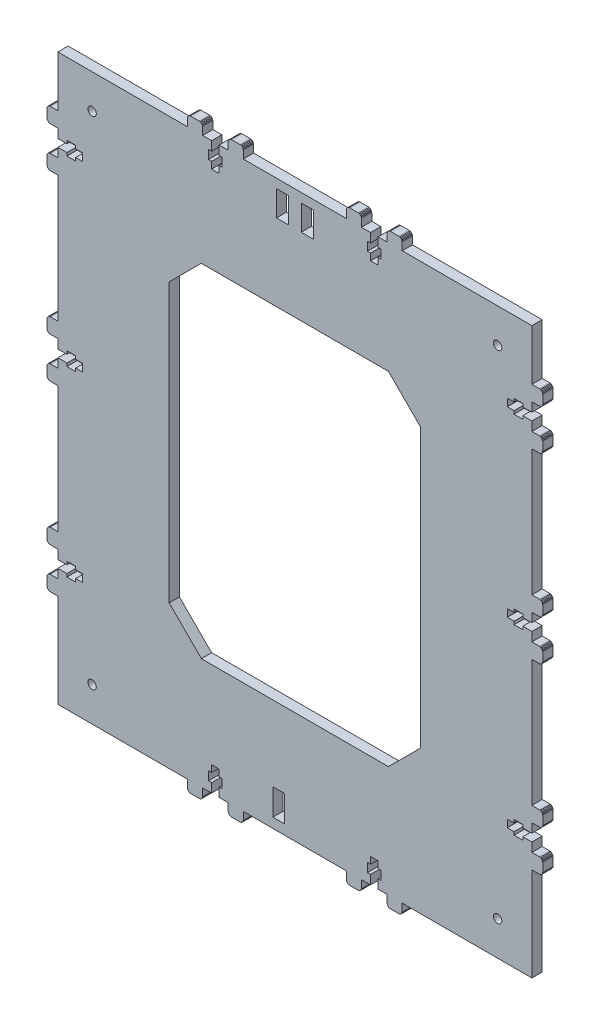
SolidWorks part; units mm, degrees
ref_plane "Plano frontal" through (0, 0, 0) normal (0, 0, 1) x (1, 0, 0)
ref_plane "Plano superior" through (0, 0, 0) normal (0, 1, 0) x (1, 0, 0)
ref_plane "Plano direito" through (0, 0, 0) normal (1, 0, 0) x (0, 0, -1)
sketch "Model" plane through (0, 0, 0) normal (0, 0, 1) x (1, 0, 0)
  line L0 (136.5926, 337.8518) -> (136.5926, 343.1518)
  line L1 (136.5926, 332.7518) -> (138.3926, 332.7518)
  line L2 (138.3926, 337.8518) -> (136.5926, 337.8518)
  line L3 (130.3926, 337.8518) -> (130.3926, 332.7518)
  line L4 (234.6925, 13.2519) -> (229.3925, 13.2519)
  line L5 (132.1926, 332.7518) -> (132.1926, 328.8018)
  line L6 (319.1925, 280.8519) -> (319.1925, 207.0019)
  line L7 (47.6926, 82.0519) -> (47.6926, 80.2519)
  line L8 (56.7426, 86.4519) -> (52.7926, 86.4519)
  line L9 (52.7926, 80.2519) -> (52.7926, 82.0519)
  line L10 (42.3926, 91.7519) -> (38.0426, 91.7519)
  line L11 (42.3926, 67.9519) -> (38.0426, 67.9519)
  line L12 (52.7926, 88.2519) -> (47.6926, 88.2519)
  line L13 (56.7426, 82.0519) -> (56.7426, 86.4519)
  line L14 (229.3925, 337.8518) -> (229.3925, 343.1518)
  line L15 (319.1925, 174.4019) -> (319.1925, 100.5519)
  line L16 (224.9925, 343.1518) -> (224.9925, 337.8518)
  line L17 (52.7926, 299.3519) -> (52.7926, 301.1519)
  line L18 (229.3925, 332.7518) -> (231.1925, 332.7518)
  line L19 (132.1926, 343.1518) -> (132.1926, 337.8518)
  line L20 (56.7426, 294.9519) -> (56.7426, 299.3519)
  line L21 (223.1925, 337.8518) -> (223.1925, 332.7518)
  line L22 (47.6926, 88.2519) -> (47.6926, 86.4519)
  line L23 (47.6926, 80.2519) -> (52.7926, 80.2519)
  line L24 (42.3926, 13.2519) -> (42.3926, 67.9519)
  line L25 (52.7926, 293.1519) -> (52.7926, 294.9519)
  line L26 (319.1925, 13.2519) -> (243.4925, 13.2519)
  line L27 (52.7926, 188.5019) -> (56.7426, 188.5019)
  line L28 (56.7426, 192.9019) -> (52.7926, 192.9019)
  line L29 (313.8925, 301.1519) -> (308.7925, 301.1519)
  line L30 (313.8925, 299.3519) -> (313.8925, 301.1519)
  line L31 (304.8425, 294.9519) -> (308.7925, 294.9519)
  line L32 (47.6926, 293.1519) -> (52.7926, 293.1519)
  line L33 (138.3926, 18.5519) -> (138.3926, 23.6519)
  line L34 (136.5926, 18.5519) -> (138.3926, 18.5519)
  line L35 (132.1926, 27.6019) -> (132.1926, 23.6519)
  line L36 (138.3926, 23.6519) -> (136.5926, 23.6519)
  line L37 (126.8926, 13.2519) -> (126.8926, 8.902)
  line L38 (150.6926, 13.2519) -> (150.6926, 8.902)
  line L39 (130.3926, 23.6519) -> (130.3926, 18.5519)
  line L40 (42.3926, 198.2019) -> (38.0426, 198.2019)
  line L41 (319.1925, 67.9519) -> (319.1925, 13.2519)
  line L42 (132.1926, 18.5519) -> (132.1926, 13.2519)
  line L43 (132.1926, 23.6519) -> (130.3926, 23.6519)
  line L44 (130.3926, 18.5519) -> (132.1926, 18.5519)
  line L45 (42.3926, 313.4519) -> (42.3926, 343.1518)
  line L46 (42.3926, 188.5019) -> (47.6926, 188.5019)
  line L47 (47.6926, 192.9019) -> (42.3926, 192.9019)
  line L48 (47.6926, 186.7019) -> (52.7926, 186.7019)
  line L49 (231.1925, 18.5519) -> (231.1925, 23.6519)
  line L50 (229.3925, 18.5519) -> (231.1925, 18.5519)
  line L51 (224.9925, 27.6019) -> (224.9925, 23.6519)
  line L52 (308.7925, 301.1519) -> (308.7925, 299.3519)
  line L53 (319.1925, 289.6519) -> (323.5425, 289.6519)
  line L54 (319.1925, 313.4518) -> (323.5425, 313.4518)
  line L55 (308.7925, 293.1519) -> (313.8925, 293.1519)
  line L56 (304.8425, 299.3519) -> (304.8425, 294.9519)
  line L57 (304.8425, 82.0519) -> (308.7925, 82.0519)
  line L58 (304.8425, 192.9019) -> (304.8425, 188.5019)
  line L59 (118.0926, 13.2519) -> (42.3926, 13.2519)
  line L60 (319.1925, 192.9019) -> (313.8925, 192.9019)
  line L61 (319.1925, 294.9519) -> (319.1925, 289.6519)
  line L62 (319.1925, 304.6519) -> (319.1925, 299.3519)
  line L63 (308.7925, 294.9519) -> (308.7925, 293.1519)
  line L64 (313.8925, 293.1519) -> (313.8925, 294.9519)
  line L65 (308.7925, 192.9019) -> (304.8425, 192.9019)
  line L66 (319.1925, 198.2019) -> (319.1925, 192.9019)
  line L67 (231.1925, 337.8518) -> (229.3925, 337.8518)
  line L68 (313.8925, 82.0519) -> (319.1925, 82.0519)
  line L69 (308.7925, 82.0519) -> (308.7925, 80.2519)
  line L70 (210.8925, 343.1518) -> (210.8925, 347.5018)
  line L71 (231.1925, 332.7518) -> (231.1925, 337.8518)
  line L72 (224.9925, 337.8518) -> (223.1925, 337.8518)
  line L73 (47.6926, 86.4519) -> (42.3926, 86.4519)
  line L74 (52.7926, 86.4519) -> (52.7926, 88.2519)
  line L75 (319.1925, 76.7519) -> (323.5425, 76.7519)
  line L76 (319.1925, 100.5519) -> (323.5425, 100.5519)
  line L77 (308.7925, 80.2519) -> (313.8925, 80.2519)
  line L78 (52.7926, 301.1519) -> (47.6926, 301.1519)
  line L79 (229.3925, 13.2519) -> (229.3925, 18.5519)
  line L80 (42.3926, 192.9019) -> (42.3926, 198.2019)
  line L81 (52.7926, 186.7019) -> (52.7926, 188.5019)
  line L82 (47.6926, 188.5019) -> (47.6926, 186.7019)
  line L83 (42.3926, 82.0519) -> (47.6926, 82.0519)
  line L84 (52.7926, 82.0519) -> (56.7426, 82.0519)
  line L85 (313.8925, 188.5019) -> (319.1925, 188.5019)
  line L86 (308.7925, 188.5019) -> (308.7925, 186.7019)
  line L87 (313.8925, 186.7019) -> (313.8925, 188.5019)
  line L88 (313.8925, 194.7019) -> (308.7925, 194.7019)
  line L89 (132.1926, 13.2519) -> (126.8926, 13.2519)
  line L90 (224.9925, 13.2519) -> (219.6925, 13.2519)
  line L91 (47.6926, 294.9519) -> (47.6926, 293.1519)
  line L92 (231.1925, 23.6519) -> (229.3925, 23.6519)
  line L93 (136.5926, 13.2519) -> (136.5926, 18.5519)
  line L94 (136.5926, 23.6519) -> (136.5926, 27.6019)
  line L95 (141.8926, 13.2519) -> (136.5926, 13.2519)
  line L96 (56.7426, 188.5019) -> (56.7426, 192.9019)
  line L97 (47.6926, 194.7019) -> (47.6926, 192.9019)
  line L98 (52.7926, 194.7019) -> (47.6926, 194.7019)
  line L99 (319.1925, 82.0519) -> (319.1925, 76.7519)
  line L100 (313.8925, 88.2519) -> (308.7925, 88.2519)
  line L101 (132.1926, 337.8518) -> (130.3926, 337.8518)
  line L102 (136.5926, 328.8018) -> (136.5926, 332.7518)
  line L103 (130.3926, 332.7518) -> (132.1926, 332.7518)
  line L104 (141.8926, 343.1518) -> (141.8926, 347.5018)
  line L105 (229.3925, 343.1518) -> (234.6925, 343.1518)
  line L106 (136.5926, 27.6019) -> (132.1926, 27.6019)
  line L107 (42.3926, 294.9519) -> (47.6926, 294.9519)
  line L108 (52.7926, 294.9519) -> (56.7426, 294.9519)
  line L109 (56.7426, 299.3519) -> (52.7926, 299.3519)
  line L110 (42.3926, 86.4519) -> (42.3926, 91.7519)
  line L111 (42.3926, 100.5519) -> (42.3926, 174.4019)
  line L112 (42.3926, 207.0019) -> (42.3926, 280.8519)
  line L113 (42.3926, 76.7519) -> (42.3926, 82.0519)
  line L114 (223.1925, 23.6519) -> (223.1925, 18.5519)
  line L115 (229.3925, 27.6019) -> (224.9925, 27.6019)
  line L116 (224.9925, 18.5519) -> (224.9925, 13.2519)
  line L117 (304.8425, 188.5019) -> (308.7925, 188.5019)
  line L118 (308.7925, 194.7019) -> (308.7925, 192.9019)
  line L119 (319.1925, 183.2019) -> (323.5425, 183.2019)
  line L120 (319.1925, 207.0019) -> (323.5425, 207.0019)
  line L121 (308.7925, 186.7019) -> (313.8925, 186.7019)
  line L122 (138.3926, 332.7518) -> (138.3926, 337.8518)
  line L123 (132.1926, 328.8018) -> (136.5926, 328.8018)
  line L124 (219.6925, 13.2519) -> (219.6925, 8.902)
  line L125 (243.4925, 13.2519) -> (243.4925, 8.902)
  line L126 (229.3925, 328.8018) -> (229.3925, 332.7518)
  line L127 (234.6925, 343.1518) -> (234.6925, 347.5018)
  line L128 (42.3926, 183.2019) -> (42.3926, 188.5019)
  line L129 (319.1925, 299.3519) -> (313.8925, 299.3519)
  line L130 (308.7925, 299.3519) -> (304.8425, 299.3519)
  line L131 (319.1925, 188.5019) -> (319.1925, 183.2019)
  line L132 (313.8925, 294.9519) -> (319.1925, 294.9519)
  line L133 (52.7926, 192.9019) -> (52.7926, 194.7019)
  line L134 (319.1925, 91.7519) -> (319.1925, 86.4519)
  line L135 (229.3925, 23.6519) -> (229.3925, 27.6019)
  line L136 (136.5926, 343.1518) -> (141.8926, 343.1518)
  line L137 (150.6926, 343.1518) -> (210.8925, 343.1518)
  line L138 (219.6925, 343.1518) -> (224.9925, 343.1518)
  line L139 (42.3926, 174.4019) -> (38.0426, 174.4019)
  line L140 (223.1925, 18.5519) -> (224.9925, 18.5519)
  line L141 (47.6926, 301.1519) -> (47.6926, 299.3519)
  line L142 (47.6926, 299.3519) -> (42.3926, 299.3519)
  line L143 (42.3926, 299.3519) -> (42.3926, 304.6519)
  line L144 (210.8925, 13.2519) -> (150.6926, 13.2519)
  line L145 (42.3926, 304.6519) -> (38.0426, 304.6519)
  line L146 (243.4925, 343.1518) -> (319.1925, 343.1518)
  line L147 (319.1925, 343.1518) -> (319.1925, 313.4518)
  line L148 (223.1925, 332.7518) -> (224.9925, 332.7518)
  line L149 (224.9925, 332.7518) -> (224.9925, 328.8018)
  line L150 (224.9925, 328.8018) -> (229.3925, 328.8018)
  line L151 (319.1925, 86.4519) -> (313.8925, 86.4519)
  line L152 (313.8925, 86.4519) -> (313.8925, 88.2519)
  line L153 (308.7925, 88.2519) -> (308.7925, 86.4519)
  line L154 (308.7925, 86.4519) -> (304.8425, 86.4519)
  line L155 (304.8425, 86.4519) -> (304.8425, 82.0519)
  line L156 (224.9925, 23.6519) -> (223.1925, 23.6519)
  line L157 (42.3926, 343.1518) -> (118.0926, 343.1518)
  line L158 (118.0926, 343.1518) -> (118.0926, 347.5018)
  line L159 (124.8926, 349.5018) -> (125.4102, 349.4337)
  line L160 (125.4102, 349.4337) -> (125.8926, 349.2339)
  line L161 (125.8926, 349.2339) -> (126.3068, 348.9161)
  line L162 (126.3068, 348.9161) -> (126.6246, 348.5018)
  line L163 (126.6246, 348.5018) -> (126.8244, 348.0195)
  line L164 (126.8926, 347.5018) -> (126.8926, 343.1518)
  line L165 (126.8244, 348.0195) -> (126.8926, 347.5018)
  line L166 (141.8926, 347.5018) -> (141.9607, 348.0195)
  line L167 (141.9607, 348.0195) -> (142.1605, 348.5018)
  line L168 (142.1605, 348.5018) -> (142.4783, 348.9161)
  line L169 (142.4783, 348.9161) -> (142.8926, 349.2339)
  line L170 (142.8926, 349.2339) -> (143.3749, 349.4337)
  line L171 (143.8926, 349.5018) -> (148.6926, 349.5018)
  line L172 (143.3749, 349.4337) -> (143.8926, 349.5018)
  line L173 (150.6926, 347.5018) -> (150.6926, 343.1518)
  line L174 (150.6926, 347.5018) -> (150.6244, 348.0195)
  line L175 (150.6244, 348.0195) -> (150.4246, 348.5018)
  line L176 (150.4246, 348.5018) -> (150.1068, 348.9161)
  line L177 (150.1068, 348.9161) -> (149.6926, 349.2339)
  line L178 (149.6926, 349.2339) -> (149.2102, 349.4337)
  line L179 (149.2102, 349.4337) -> (148.6926, 349.5018)
  line L180 (118.0926, 347.5018) -> (118.1607, 348.0195)
  line L181 (118.1607, 348.0195) -> (118.3605, 348.5018)
  line L182 (118.3605, 348.5018) -> (118.6784, 348.9161)
  line L183 (118.6784, 348.9161) -> (119.0926, 349.2339)
  line L184 (119.0926, 349.2339) -> (119.5749, 349.4337)
  line L185 (120.0926, 349.5018) -> (124.8926, 349.5018)
  line L186 (119.5749, 349.4337) -> (120.0926, 349.5018)
  line L187 (234.6925, 347.5018) -> (234.7607, 348.0195)
  line L188 (234.7607, 348.0195) -> (234.9605, 348.5018)
  line L189 (234.9605, 348.5018) -> (235.2783, 348.9161)
  line L190 (235.2783, 348.9161) -> (235.6925, 349.2339)
  line L191 (235.6925, 349.2339) -> (236.1749, 349.4337)
  line L192 (236.6925, 349.5018) -> (241.4925, 349.5018)
  line L193 (236.1749, 349.4337) -> (236.6925, 349.5018)
  line L194 (243.4925, 347.5018) -> (243.4925, 343.1518)
  line L195 (243.4925, 347.5018) -> (243.4244, 348.0195)
  line L196 (243.4244, 348.0195) -> (243.2246, 348.5018)
  line L197 (243.2246, 348.5018) -> (242.9067, 348.9161)
  line L198 (242.9067, 348.9161) -> (242.4925, 349.2339)
  line L199 (242.4925, 349.2339) -> (242.0102, 349.4337)
  line L200 (242.0102, 349.4337) -> (241.4925, 349.5018)
  line L201 (219.6925, 347.5018) -> (219.6925, 343.1518)
  line L202 (219.6925, 347.5018) -> (219.6244, 348.0195)
  line L203 (219.6244, 348.0195) -> (219.4246, 348.5018)
  line L204 (219.4246, 348.5018) -> (219.1068, 348.9161)
  line L205 (219.1068, 348.9161) -> (218.6925, 349.2339)
  line L206 (218.6925, 349.2339) -> (218.2102, 349.4337)
  line L207 (218.2102, 349.4337) -> (217.6925, 349.5018)
  line L208 (210.8925, 347.5018) -> (210.9607, 348.0195)
  line L209 (210.9607, 348.0195) -> (211.1605, 348.5018)
  line L210 (211.1605, 348.5018) -> (211.4783, 348.9161)
  line L211 (211.4783, 348.9161) -> (211.8925, 349.2339)
  line L212 (211.8925, 349.2339) -> (212.3749, 349.4337)
  line L213 (212.8925, 349.5018) -> (217.6925, 349.5018)
  line L214 (212.3749, 349.4337) -> (212.8925, 349.5018)
  line L215 (210.8925, 8.902) -> (210.8925, 13.2519)
  line L216 (210.8925, 8.902) -> (210.9607, 8.3843)
  line L217 (210.9607, 8.3843) -> (211.1605, 7.902)
  line L218 (211.1605, 7.902) -> (211.4783, 7.4877)
  line L219 (211.4783, 7.4877) -> (211.8925, 7.1699)
  line L220 (211.8925, 7.1699) -> (212.3749, 6.9701)
  line L221 (212.3749, 6.9701) -> (212.8925, 6.902)
  line L222 (219.6925, 8.902) -> (219.6244, 8.3843)
  line L223 (219.6244, 8.3843) -> (219.4246, 7.902)
  line L224 (219.4246, 7.902) -> (219.1067, 7.4877)
  line L225 (219.1067, 7.4877) -> (218.6925, 7.1699)
  line L226 (218.6925, 7.1699) -> (218.2102, 6.9701)
  line L227 (217.6925, 6.902) -> (212.8925, 6.902)
  line L228 (218.2102, 6.9701) -> (217.6925, 6.902)
  line L229 (323.5425, 174.4019) -> (319.1925, 174.4019)
  line L230 (323.5425, 174.4019) -> (324.0601, 174.47)
  line L231 (324.0601, 174.47) -> (324.5425, 174.6698)
  line L232 (324.5425, 174.6698) -> (324.9567, 174.9877)
  line L233 (324.9567, 174.9877) -> (325.2746, 175.4019)
  line L234 (325.2746, 175.4019) -> (325.4744, 175.8843)
  line L235 (325.4744, 175.8843) -> (325.5425, 176.4019)
  line L236 (325.5425, 93.7519) -> (325.4744, 93.2343)
  line L237 (325.4744, 93.2343) -> (325.2746, 92.7519)
  line L238 (325.2746, 92.7519) -> (324.9567, 92.3377)
  line L239 (324.9567, 92.3377) -> (324.5425, 92.0199)
  line L240 (324.5425, 92.0199) -> (324.0601, 91.8201)
  line L241 (323.5425, 91.7519) -> (319.1925, 91.7519)
  line L242 (324.0601, 91.8201) -> (323.5425, 91.7519)
  line L243 (36.0426, 93.7519) -> (36.0426, 98.5519)
  line L244 (36.0426, 93.7519) -> (36.1107, 93.2343)
  line L245 (36.1107, 93.2343) -> (36.3105, 92.7519)
  line L246 (36.3105, 92.7519) -> (36.6284, 92.3377)
  line L247 (36.6284, 92.3377) -> (37.0426, 92.0199)
  line L248 (37.0426, 92.0199) -> (37.525, 91.8201)
  line L249 (37.525, 91.8201) -> (38.0426, 91.7519)
  line L250 (38.0426, 67.9519) -> (37.525, 68.0201)
  line L251 (37.525, 68.0201) -> (37.0426, 68.2199)
  line L252 (37.0426, 68.2199) -> (36.6284, 68.5377)
  line L253 (36.6284, 68.5377) -> (36.3105, 68.9519)
  line L254 (36.3105, 68.9519) -> (36.1107, 69.4343)
  line L255 (36.0426, 69.9519) -> (36.0426, 74.7519)
  line L256 (36.1107, 69.4343) -> (36.0426, 69.9519)
  line L257 (38.0426, 76.7519) -> (42.3926, 76.7519)
  line L258 (38.0426, 76.7519) -> (37.525, 76.6838)
  line L259 (37.525, 76.6838) -> (37.0426, 76.484)
  line L260 (37.0426, 76.484) -> (36.6284, 76.1661)
  line L261 (36.6284, 76.1661) -> (36.3105, 75.7519)
  line L262 (36.3105, 75.7519) -> (36.1107, 75.2696)
  line L263 (36.1107, 75.2696) -> (36.0426, 74.7519)
  line L264 (36.0426, 306.6519) -> (36.0426, 311.4519)
  line L265 (36.0426, 306.6519) -> (36.1107, 306.1342)
  line L266 (36.1107, 306.1342) -> (36.3105, 305.6519)
  line L267 (36.3105, 305.6519) -> (36.6284, 305.2376)
  line L268 (36.6284, 305.2376) -> (37.0426, 304.9198)
  line L269 (37.0426, 304.9198) -> (37.525, 304.72)
  line L270 (37.525, 304.72) -> (38.0426, 304.6519)
  line L271 (325.5425, 69.9519) -> (325.4744, 69.4343)
  line L272 (325.4744, 69.4343) -> (325.2746, 68.9519)
  line L273 (325.2746, 68.9519) -> (324.9567, 68.5377)
  line L274 (324.9567, 68.5377) -> (324.5425, 68.2199)
  line L275 (324.5425, 68.2199) -> (324.0601, 68.0201)
  line L276 (323.5425, 67.9519) -> (319.1925, 67.9519)
  line L277 (324.0601, 68.0201) -> (323.5425, 67.9519)
  line L278 (124.8926, 6.902) -> (120.0926, 6.902)
  line L279 (124.8926, 6.902) -> (125.4102, 6.9701)
  line L280 (125.4102, 6.9701) -> (125.8926, 7.1699)
  line L281 (125.8926, 7.1699) -> (126.3068, 7.4877)
  line L282 (126.3068, 7.4877) -> (126.6246, 7.902)
  line L283 (126.6246, 7.902) -> (126.8244, 8.3843)
  line L284 (126.8244, 8.3843) -> (126.8926, 8.902)
  line L285 (118.0926, 8.902) -> (118.0926, 13.2519)
  line L286 (118.0926, 8.902) -> (118.1607, 8.3843)
  line L287 (118.1607, 8.3843) -> (118.3605, 7.902)
  line L288 (118.3605, 7.902) -> (118.6784, 7.4877)
  line L289 (118.6784, 7.4877) -> (119.0926, 7.1699)
  line L290 (119.0926, 7.1699) -> (119.5749, 6.9701)
  line L291 (119.5749, 6.9701) -> (120.0926, 6.902)
  line L292 (38.0426, 100.5519) -> (42.3926, 100.5519)
  line L293 (38.0426, 100.5519) -> (37.525, 100.4838)
  line L294 (37.525, 100.4838) -> (37.0426, 100.284)
  line L295 (37.0426, 100.284) -> (36.6284, 99.9661)
  line L296 (36.6284, 99.9661) -> (36.3105, 99.5519)
  line L297 (36.3105, 99.5519) -> (36.1107, 99.0696)
  line L298 (36.1107, 99.0696) -> (36.0426, 98.5519)
  line L299 (323.5425, 304.6519) -> (319.1925, 304.6519)
  line L300 (323.5425, 304.6519) -> (324.0601, 304.72)
  line L301 (324.0601, 304.72) -> (324.5425, 304.9198)
  line L302 (324.5425, 304.9198) -> (324.9567, 305.2376)
  line L303 (324.9567, 305.2376) -> (325.2746, 305.6519)
  line L304 (325.2746, 305.6519) -> (325.4744, 306.1342)
  line L305 (325.4744, 306.1342) -> (325.5425, 306.6519)
  line L306 (325.5425, 287.6519) -> (325.5425, 282.8519)
  line L307 (325.5425, 287.6519) -> (325.4744, 288.1695)
  line L308 (325.4744, 288.1695) -> (325.2746, 288.6519)
  line L309 (325.2746, 288.6519) -> (324.9567, 289.0661)
  line L310 (324.9567, 289.0661) -> (324.5425, 289.3839)
  line L311 (324.5425, 289.3839) -> (324.0601, 289.5837)
  line L312 (324.0601, 289.5837) -> (323.5425, 289.6519)
  line L313 (323.5425, 280.8519) -> (319.1925, 280.8519)
  line L314 (323.5425, 280.8519) -> (324.0601, 280.92)
  line L315 (324.0601, 280.92) -> (324.5425, 281.1198)
  line L316 (324.5425, 281.1198) -> (324.9567, 281.4377)
  line L317 (324.9567, 281.4377) -> (325.2746, 281.8519)
  line L318 (325.2746, 281.8519) -> (325.4744, 282.3342)
  line L319 (325.4744, 282.3342) -> (325.5425, 282.8519)
  line L320 (148.6926, 6.902) -> (143.8926, 6.902)
  line L321 (148.6926, 6.902) -> (149.2102, 6.9701)
  line L322 (149.2102, 6.9701) -> (149.6926, 7.1699)
  line L323 (149.6926, 7.1699) -> (150.1068, 7.4877)
  line L324 (150.1068, 7.4877) -> (150.4246, 7.902)
  line L325 (150.4246, 7.902) -> (150.6244, 8.3843)
  line L326 (150.6244, 8.3843) -> (150.6926, 8.902)
  line L327 (36.0426, 200.2019) -> (36.0426, 205.0019)
  line L328 (36.0426, 200.2019) -> (36.1107, 199.6843)
  line L329 (36.1107, 199.6843) -> (36.3105, 199.2019)
  line L330 (36.3105, 199.2019) -> (36.6284, 198.7877)
  line L331 (36.6284, 198.7877) -> (37.0426, 198.4698)
  line L332 (37.0426, 198.4698) -> (37.525, 198.27)
  line L333 (37.525, 198.27) -> (38.0426, 198.2019)
  line L334 (141.8926, 8.902) -> (141.8926, 13.2519)
  line L335 (141.8926, 8.902) -> (141.9607, 8.3843)
  line L336 (141.9607, 8.3843) -> (142.1605, 7.902)
  line L337 (142.1605, 7.902) -> (142.4783, 7.4877)
  line L338 (142.4783, 7.4877) -> (142.8926, 7.1699)
  line L339 (142.8926, 7.1699) -> (143.3749, 6.9701)
  line L340 (143.3749, 6.9701) -> (143.8926, 6.902)
  line L341 (38.0426, 207.0019) -> (42.3926, 207.0019)
  line L342 (38.0426, 207.0019) -> (37.525, 206.9337)
  line L343 (37.525, 206.9337) -> (37.0426, 206.7339)
  line L344 (37.0426, 206.7339) -> (36.6284, 206.4161)
  line L345 (36.6284, 206.4161) -> (36.3105, 206.0019)
  line L346 (36.3105, 206.0019) -> (36.1107, 205.5195)
  line L347 (36.1107, 205.5195) -> (36.0426, 205.0019)
  line L348 (38.0426, 313.4519) -> (42.3926, 313.4519)
  line L349 (38.0426, 313.4519) -> (37.525, 313.3837)
  line L350 (37.525, 313.3837) -> (37.0426, 313.1839)
  line L351 (37.0426, 313.1839) -> (36.6284, 312.8661)
  line L352 (36.6284, 312.8661) -> (36.3105, 312.4519)
  line L353 (36.3105, 312.4519) -> (36.1107, 311.9695)
  line L354 (36.1107, 311.9695) -> (36.0426, 311.4519)
  line L355 (38.0426, 289.6519) -> (42.3926, 289.6519)
  line L356 (38.0426, 289.6519) -> (37.525, 289.5837)
  line L357 (37.525, 289.5837) -> (37.0426, 289.3839)
  line L358 (37.0426, 289.3839) -> (36.6284, 289.0661)
  line L359 (36.6284, 289.0661) -> (36.3105, 288.6519)
  line L360 (36.3105, 288.6519) -> (36.1107, 288.1695)
  line L361 (36.1107, 288.1695) -> (36.0426, 287.6519)
  line L362 (323.5425, 313.4518) -> (324.0601, 313.3837)
  line L363 (324.0601, 313.3837) -> (324.5425, 313.1839)
  line L364 (324.5425, 313.1839) -> (324.9567, 312.8661)
  line L365 (324.9567, 312.8661) -> (325.2746, 312.4518)
  line L366 (325.2746, 312.4518) -> (325.4744, 311.9695)
  line L367 (325.5425, 311.4518) -> (325.5425, 306.6519)
  line L368 (325.4744, 311.9695) -> (325.5425, 311.4518)
  line L369 (236.6925, 6.902) -> (236.1749, 6.9701)
  line L370 (236.1749, 6.9701) -> (235.6925, 7.1699)
  line L371 (235.6925, 7.1699) -> (235.2783, 7.4877)
  line L372 (235.2783, 7.4877) -> (234.9605, 7.902)
  line L373 (234.9605, 7.902) -> (234.7607, 8.3843)
  line L374 (234.6925, 8.902) -> (234.6925, 13.2519)
  line L375 (234.7607, 8.3843) -> (234.6925, 8.902)
  line L376 (325.5425, 74.7519) -> (325.5425, 69.9519)
  line L377 (325.5425, 74.7519) -> (325.4744, 75.2696)
  line L378 (325.4744, 75.2696) -> (325.2746, 75.7519)
  line L379 (325.2746, 75.7519) -> (324.9567, 76.1661)
  line L380 (324.9567, 76.1661) -> (324.5425, 76.484)
  line L381 (324.5425, 76.484) -> (324.0601, 76.6838)
  line L382 (324.0601, 76.6838) -> (323.5425, 76.7519)
  line L383 (323.5425, 100.5519) -> (324.0601, 100.4838)
  line L384 (324.0601, 100.4838) -> (324.5425, 100.284)
  line L385 (324.5425, 100.284) -> (324.9567, 99.9661)
  line L386 (324.9567, 99.9661) -> (325.2746, 99.5519)
  line L387 (325.2746, 99.5519) -> (325.4744, 99.0696)
  line L388 (325.5425, 98.5519) -> (325.5425, 93.7519)
  line L389 (325.4744, 99.0696) -> (325.5425, 98.5519)
  line L390 (325.5425, 200.2019) -> (325.4744, 199.6842)
  line L391 (325.4744, 199.6842) -> (325.2746, 199.2019)
  line L392 (325.2746, 199.2019) -> (324.9567, 198.7877)
  line L393 (324.9567, 198.7877) -> (324.5425, 198.4698)
  line L394 (324.5425, 198.4698) -> (324.0601, 198.27)
  line L395 (323.5425, 198.2019) -> (319.1925, 198.2019)
  line L396 (324.0601, 198.27) -> (323.5425, 198.2019)
  line L397 (323.5425, 183.2019) -> (324.0601, 183.1337)
  line L398 (324.0601, 183.1337) -> (324.5425, 182.9339)
  line L399 (324.5425, 182.9339) -> (324.9567, 182.6161)
  line L400 (324.9567, 182.6161) -> (325.2746, 182.2019)
  line L401 (325.2746, 182.2019) -> (325.4744, 181.7195)
  line L402 (325.5425, 181.2019) -> (325.5425, 176.4019)
  line L403 (325.4744, 181.7195) -> (325.5425, 181.2019)
  line L404 (38.0426, 183.2019) -> (42.3926, 183.2019)
  line L405 (38.0426, 183.2019) -> (37.525, 183.1338)
  line L406 (37.525, 183.1338) -> (37.0426, 182.9339)
  line L407 (37.0426, 182.9339) -> (36.6284, 182.6161)
  line L408 (36.6284, 182.6161) -> (36.3105, 182.2019)
  line L409 (36.3105, 182.2019) -> (36.1107, 181.7195)
  line L410 (36.1107, 181.7195) -> (36.0426, 181.2019)
  line L411 (241.4925, 6.902) -> (236.6925, 6.902)
  line L412 (241.4925, 6.902) -> (242.0102, 6.9701)
  line L413 (242.0102, 6.9701) -> (242.4925, 7.1699)
  line L414 (242.4925, 7.1699) -> (242.9067, 7.4877)
  line L415 (242.9067, 7.4877) -> (243.2246, 7.902)
  line L416 (243.2246, 7.902) -> (243.4244, 8.3843)
  line L417 (243.4244, 8.3843) -> (243.4925, 8.902)
  line L418 (323.5425, 207.0019) -> (324.0601, 206.9337)
  line L419 (324.0601, 206.9337) -> (324.5425, 206.7339)
  line L420 (324.5425, 206.7339) -> (324.9567, 206.4161)
  line L421 (324.9567, 206.4161) -> (325.2746, 206.0019)
  line L422 (325.2746, 206.0019) -> (325.4744, 205.5195)
  line L423 (325.5425, 205.0019) -> (325.5425, 200.2019)
  line L424 (325.4744, 205.5195) -> (325.5425, 205.0019)
  line L425 (36.0426, 176.4019) -> (36.0426, 181.2019)
  line L426 (36.0426, 176.4019) -> (36.1107, 175.8843)
  line L427 (36.1107, 175.8843) -> (36.3105, 175.4019)
  line L428 (36.3105, 175.4019) -> (36.6284, 174.9877)
  line L429 (36.6284, 174.9877) -> (37.0426, 174.6699)
  line L430 (37.0426, 174.6699) -> (37.525, 174.4701)
  line L431 (37.525, 174.4701) -> (38.0426, 174.4019)
  line L432 (36.0426, 282.8519) -> (36.0426, 287.6519)
  line L433 (36.0426, 282.8519) -> (36.1107, 282.3342)
  line L434 (36.1107, 282.3342) -> (36.3105, 281.8519)
  line L435 (36.3105, 281.8519) -> (36.6284, 281.4377)
  line L436 (36.6284, 281.4377) -> (37.0426, 281.1198)
  line L437 (37.0426, 281.1198) -> (37.525, 280.92)
  line L438 (37.525, 280.92) -> (38.0426, 280.8519)
  line L439 (42.3926, 280.8519) -> (38.0426, 280.8519)
  line L440 (313.8925, 192.9019) -> (313.8925, 194.7019)
  line L441 (42.3926, 289.6519) -> (42.3926, 294.9519)
  line L442 (126.8926, 343.1518) -> (132.1926, 343.1518)
  line L443 (313.8925, 80.2519) -> (313.8925, 82.0519)
  line L444 (191.5425, 323.0519) -> (184.5425, 323.0519)
  line L445 (184.5425, 323.0519) -> (184.5425, 337.8518)
  line L446 (184.5425, 337.8518) -> (191.5425, 337.8518)
  line L447 (191.5425, 337.8518) -> (191.5425, 323.0519)
  line L448 (170.0426, 337.8518) -> (177.0425, 337.8518)
  line L449 (177.0425, 337.8518) -> (177.0425, 323.0519)
  line L450 (177.0425, 323.0519) -> (170.0426, 323.0519)
  line L451 (170.0426, 323.0519) -> (170.0426, 337.8518)
  line L452 (167.9426, 18.9519) -> (167.9426, 34.3519)
  line L453 (167.9426, 34.3519) -> (174.8425, 34.3519)
  line L454 (174.8425, 34.3519) -> (174.8425, 18.9519)
  line L455 (174.8425, 18.9519) -> (167.9426, 18.9519)
  line L456 (254.1925, 97.0387) -> (254.1925, 259.365)
  line L457 (254.1925, 259.365) -> (235.4057, 278.1518)
  line L458 (235.4057, 278.1518) -> (126.1794, 278.1518)
  line L459 (126.1794, 278.1518) -> (107.3926, 259.365)
  line L460 (107.3926, 259.365) -> (107.3926, 97.0387)
  line L461 (107.3926, 97.0387) -> (126.1794, 78.2519)
  line L462 (126.1794, 78.2519) -> (235.4057, 78.2519)
  line L463 (235.4057, 78.2519) -> (254.1925, 97.0387)
  circle A0 centre (299.1925, 323.1518) radius 2.45
  circle A1 centre (299.1925, 33.2519) radius 2.45
  circle A2 centre (62.3926, 33.2519) radius 2.45
  circle A3 centre (62.3926, 323.1518) radius 2.45
extrude "Ressalto-extrusão1" add sketch "Model" along normal blind 6
ref_plane "Plano1" through (0, 26.6519, 0) normal (0, 1, 0) x (1, 0, 0)
